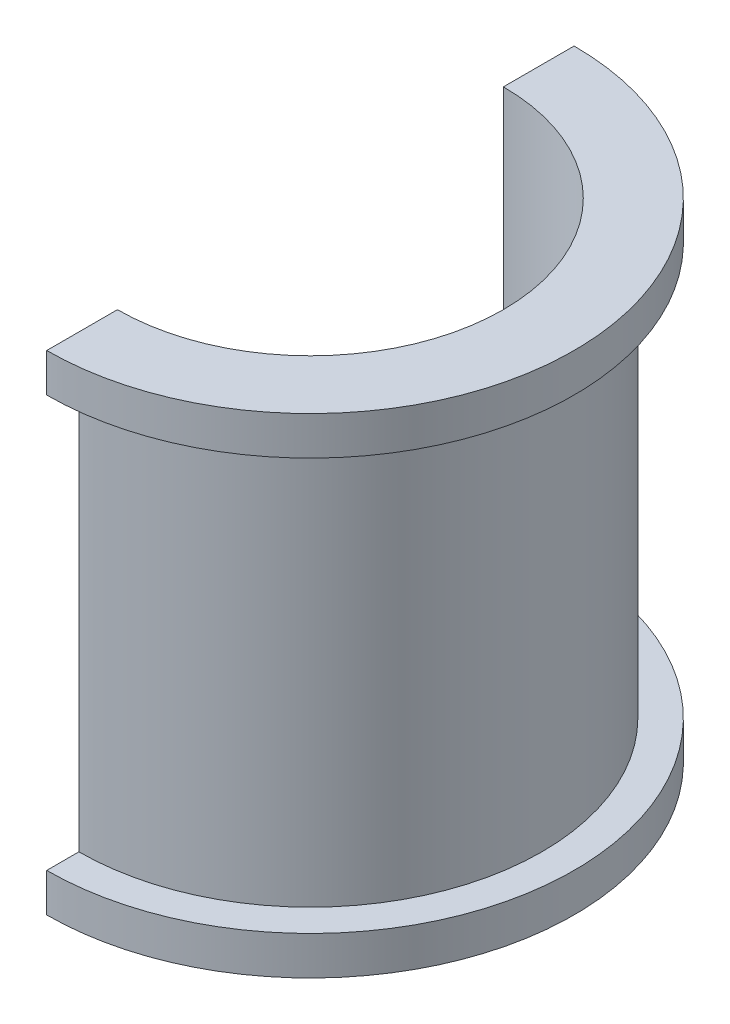
SolidWorks part; units mm, degrees
ref_plane "Ebene vorne" through (0, 0, 0) normal (0, 0, 1) x (1, 0, 0)
ref_plane "Ebene oben" through (0, 0, 0) normal (0, 1, 0) x (1, 0, 0)
ref_plane "Ebene rechts" through (0, 0, 0) normal (1, 0, 0) x (0, 0, -1)
sketch "Sketch1" plane through (0, 0, 0) normal (0, 1, 0) x (1, 0, 0)
  circle A0 centre (0, 0) radius 18
  circle A1 centre (0, 0) radius 15
  dimension "D1" = 30
  dimension "D2" = 36
extrude "Boss-Extrude1" add sketch "Sketch1" along normal blind 35
sketch "Sketch2" plane through (0, 0, 0) normal (0, 1, 0) x (1, 0, 0)
  circle A0 centre (0, 0) radius 20.5
  circle A1 centre (0, 0) radius 15
  dimension "D1" = 30
  dimension "D2" = 41
extrude "Boss-Extrude2" add sketch "Sketch2" along normal blind 3
ref_plane "Plane1" through (0, 35, 0) normal (0, 1, 0) x (1, 0, 0)
sketch "Sketch3" plane through (0, 35, 0) normal (0, 1, 0) x (1, 0, 0)
  circle A0 centre (0, 0) radius 20.5
  circle A1 centre (0, 0) radius 15
  dimension "D1" = 30
  dimension "D2" = 41
extrude "Boss-Extrude3" add sketch "Sketch3" along normal blind 3
extrude "Boss-Extrude4" add sketch "Sketch2<2>" along normal blind 3
sketch "Sketch2<2>" plane through (0, 0, 0) normal (0, 1, 0) x (1, 0, 0) same geometry as "Sketch2"
split "Split1" trim tools "Ebene rechts" bodies to split 106 resulting bodies 105
